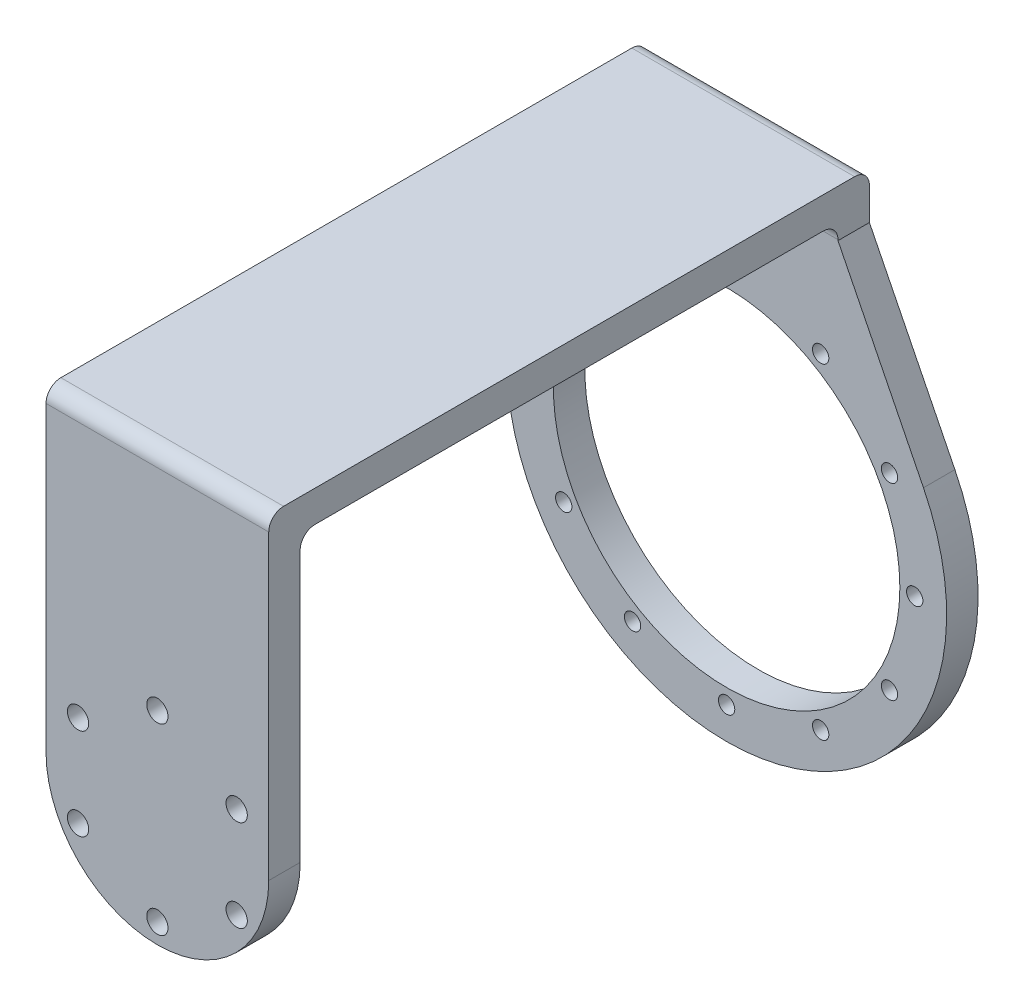
SolidWorks part; units mm, degrees
note: The reader was unsure of these and kept them because the rebuilt part matched: shared geometry of "Sketch2<4>", "Sketch4<4>".
ref_plane "Front Plane" through (0, 0, 0) normal (0, 0, 1) x (1, 0, 0)
ref_plane "Top Plane" through (0, 0, 0) normal (0, 1, 0) x (1, 0, 0)
ref_plane "Right Plane" through (0, 0, 0) normal (1, 0, 0) x (0, 0, -1)
sketch "Sketch2" plane through (0, 0, 0) normal (0, 0, 1) x (1, 0, 0)
  line L0 (0, 38) -> (0, 0) construction
  line L1 (0, 18.5) -> (0, 0) construction
  line L3 (0, 0) -> (-16.0215, -9.25) construction
  line L5 (0, 0) -> (16.0215, 9.25) construction
  line L6 (0, 0) -> (0, -18.5) construction
  line L7 (0, 0) -> (-16.0215, 9.25) construction
  line L8 (0, 0) -> (18.5, 0) construction
  line L9 (0, 0) -> (16.0215, -9.25) construction
  circle A0 centre (0, 0) radius 38 construction
  circle A1 centre (0, 0) radius 44.45
  circle A2 centre (0, 0) radius 35
  circle A3 centre (0, 0) radius 18.5
  circle A4 centre (0, 0) radius 22.5
  circle A5 centre (0, 18.5) radius 2.15
  circle A6 centre (16.0215, 9.25) radius 2.15
  circle A8 centre (16.0215, -9.25) radius 2.15
  circle A9 centre (-16.0215, 9.25) radius 2.15
  circle A10 centre (-16.0215, -9.25) radius 2.15
  circle A11 centre (0, -18.5) radius 2.15
  point P3 (0, 38)
  point P4 (19, 32.909)
  point P7 (32.909, 19)
  point P8 (38, 0)
  point P9 (32.909, -19)
  point P10 (19, -32.909)
  point P11 (0, -38)
  point P12 (-19, -32.909)
  point P13 (-32.909, -19)
  point P14 (-38, 0)
  point P15 (-32.909, 19)
  point P16 (-19, 32.909)
  point P17 (0, 0)
  point P21 (0, 18.5)
  dimension "D1" = 76
  dimension "D3" = 88.9
  dimension "D4" = 3
  dimension "D5" = 37
  dimension "D7" = 45
  dimension "D9" = 4.3
  dimension "D6" = 30
  dimension "D8" = 30
  dimension "D2" = 12
extrude "Boss-Extrude1" add sketch "Sketch2" along normal blind 6.35 from offset 115 contours A3 | A4 A3
extrude "Boss-Extrude2" add sketch "Sketch2<4>" along normal blind 6.35 separate body contours A1 A2
sketch "Sketch2<4>" plane through (0, 0, 0) normal (0, 0, 1) x (1, 0, 0) same geometry as "Sketch2"
hole_wizard "M4x0.7 Tapped Hole1" positions "3DSketch1" profile "Sketch3" tap size "M4x0.7" standard "ANSI Metric" end condition through all
sketch3d "3DSketch1"
  point P0 (0, 38, 6.35)
sketch "Sketch3" plane through (0, 38, 6.35) normal (1, 0, 0) x (0, -1, 0)
  line L0 (0, 0) -> (0, 6.35)
  line L1 (0, 6.35) -> (1.65, 6.35)
  line L2 (1.65, 6.35) -> (1.65, 0)
  line L5 (1.65, 0) -> (0, 0)
  line L11 (0, -6.35) -> (0, 107.95) construction
  dimension "Thru Tap Drill Dia." = 3.3
  dimension "Thru Tap Drill Depth" = 6.35
cosmetic thread "Hole Thread1" parameters "D2"=4
pattern_circular "CirPattern1" count 12 over 360 about axis through (0, 0, 0) along (0, 0, 1) of "M4x0.7 Tapped Hole1"
cosmetic thread "Hole Thread2" parameters "D2"=4
cosmetic thread "Hole Thread3" parameters "D2"=4
cosmetic thread "Hole Thread4" parameters "D2"=4
cosmetic thread "Hole Thread5" parameters "D2"=4
cosmetic thread "Hole Thread6" parameters "D2"=4
cosmetic thread "Hole Thread7" parameters "D2"=4
cosmetic thread "Hole Thread8" parameters "D2"=4
cosmetic thread "Hole Thread9" parameters "D2"=4
cosmetic thread "Hole Thread10" parameters "D2"=4
cosmetic thread "Hole Thread11" parameters "D2"=4
cosmetic thread "Hole Thread12" parameters "D2"=4
sketch "Sketch4" plane through (0, 0, 0) normal (0, 0, 1) x (1, 0, 0)
  line L0 (-22.5, 0) -> (-22.5, 54.45)
  line L1 (-22.5, 54.45) -> (22.5, 54.45)
  line L2 (22.5, 54.45) -> (22.5, 0)
  line L3 (-39.7703, 19.8525) -> (-22.5, 54.45)
  line L4 (-22.5, 54.45) -> (22.5, 54.45)
  line L5 (22.5, 54.45) -> (39.7703, 19.8525)
  circle A0 centre (0, 0) radius 22.5 construction
  circle A1 centre (0, 0) radius 44.45 construction
  arc A2 (-22.5, 0) -> (22.5, 0) centre (0, 0) cw
  arc A3 (-39.7703, 19.8525) -> (39.7703, 19.8525) centre (0, 0) cw
  point P16 (0, 44.45)
  dimension "D2" = 10
extrude "Boss-Extrude3" add sketch "Sketch4" along normal blind 6.35 contours A3 L5 L4 L3
extrude "Boss-Extrude4" add sketch "Sketch4<4>" along normal blind 6.35 from offset 115 contours L0 A3 L2 L1 | A3 L0 A2 L2
sketch "Sketch4<4>" plane through (0, 0, 0) normal (0, 0, 1) x (1, 0, 0) same geometry as "Sketch4"
sketch "Sketch5" plane through (0, 0, 0) normal (1, 0, 0) x (0, 0, -1)
  line L0 (0, 54.45) -> (0, 60.975)
  line L1 (-3, 63.975) -> (-118.35, 63.975)
  line L2 (-121.35, 60.975) -> (-121.35, 54.45)
  line L3 (-121.35, 54.45) -> (-121.35, 0) construction
  line L4 (-115, 54.45) -> (-115, 54.625)
  line L5 (-112, 57.625) -> (-9.35, 57.625)
  line L6 (-6.35, 54.625) -> (-6.35, 54.45)
  line L7 (-121.35, 54.45) -> (-115, 54.45)
  line L8 (-6.35, 54.45) -> (0, 54.45)
  arc A0 (0, 60.975) -> (-3, 63.975) centre (-3, 60.975) ccw
  arc A1 (-9.35, 57.625) -> (-6.35, 54.625) centre (-9.35, 54.625) cw
  arc A2 (-115, 54.625) -> (-112, 57.625) centre (-112, 54.625) cw
  arc A3 (-118.35, 63.975) -> (-121.35, 60.975) centre (-118.35, 60.975) ccw
  point P20 (-6.35, 57.625)
  dimension "D3" = 3
  dimension "D1" = 6.35
  dimension "D2" = 3.175
extrude "Boss-Extrude5" add sketch "Sketch5" along normal up to vertex (22.5 mm away) and the other way up to vertex (22.5 mm away)
equation "\"Height\"=115"
equation "\"D19@Boss-Extrude3\"=\"Height\""
equation "\"D19@Boss-Extrude1\"=\"Height\""
equation "\"D19@Boss-Extrude4\"=\"Height\""
